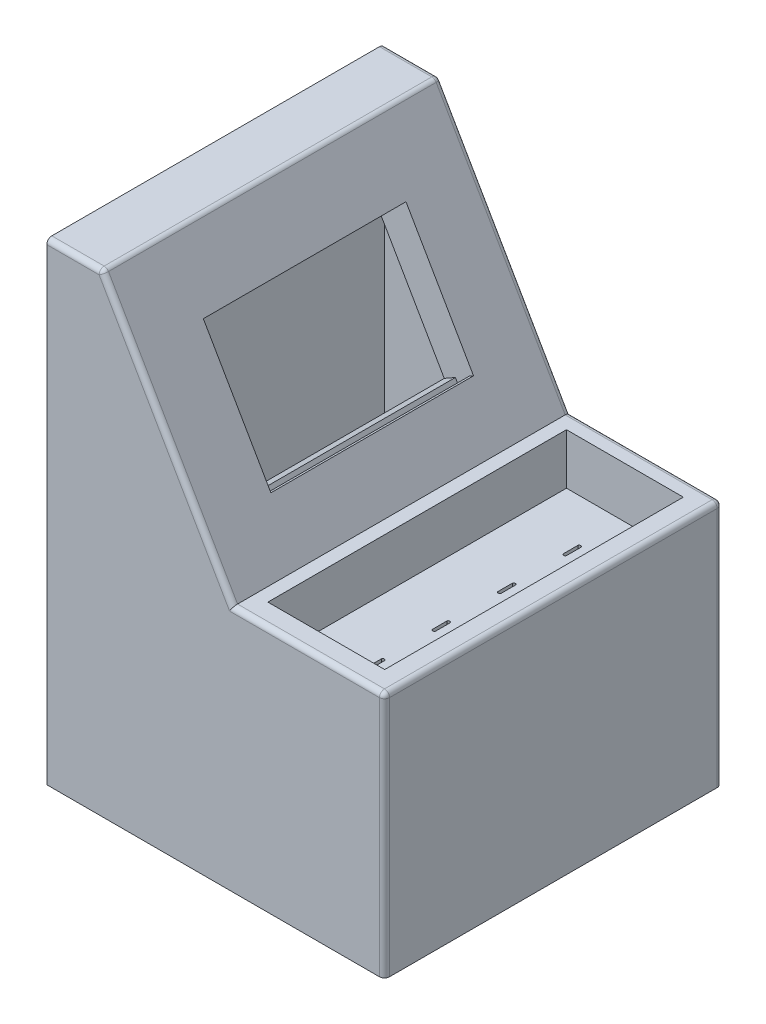
SolidWorks part; units mm, degrees
material "Polyethylene Cross-Linked"
ref_plane "Front Plane" through (0, 0, 0) normal (0, 0, 1) x (1, 0, 0)
ref_plane "Top Plane" through (0, 0, 0) normal (0, 1, 0) x (1, 0, 0)
ref_plane "Right Plane" through (0, 0, 0) normal (1, 0, 0) x (0, 0, -1)
sketch "Sketch1" plane through (0, 0, 0) normal (0, 0, 1) x (1, 0, 0)
  line L0 (0, 203.2) -> (0, 711.2)
  line L1 (0, 0) -> (508, 0)
  line L2 (0, 0) -> (0, 203.2)
  line L3 (0, 203.2) -> (508, 203.2)
  line L4 (508, 0) -> (508, 203.2)
  line L5 (0, 711.2) -> (83.1288, 711.2)
  line L6 (83.1288, 711.2) -> (279.4, 371.2483)
  line L7 (279.4, 371.2483) -> (508, 371.2483)
  line L8 (508, 371.2483) -> (508, 203.2)
  dimension "D1" = 508
  dimension "D2" = 508
  dimension "D3" = 203.2
  dimension "D4" = 120
  dimension "D5" = 392.5424
  dimension "D6" = 228.6
extrude "Boss-Extrude1" add sketch "Sketch1" along normal blind 508 contours L8 L7 L6 L5 L0 L3 | L2 L1 L4 L3 region at (189.225, 380.8468, 0)
sketch "Sketch2" plane through (0, 371.2483, 0) normal (0, 1, 0) x (1, 0, 0)
  line L1 (299.6447, -25.9057) -> (475.366, -25.9057)
  line L2 (299.6447, -25.9057) -> (299.6447, -475.0665)
  line L3 (299.6447, -475.0665) -> (475.366, -475.0665)
  line L4 (475.366, -25.9057) -> (475.366, -475.0665)
extrude "Cut-Extrude1" cut sketch "Sketch2" against normal blind 76.2
sketch "Sketch3" plane through (370.3053, 213.7958, 0) normal (0.866, 0.5, 0) x (0, 0, -1)
  line L0 (0, 574.3529) -> (0, 181.8105) construction
  line L1 (-406.4, 472.7529) -> (-101.6, 472.7529)
  line L2 (-406.4, 472.7529) -> (-406.4, 269.5529)
  line L3 (-406.4, 269.5529) -> (-101.6, 269.5529)
  line L4 (-101.6, 472.7529) -> (-101.6, 269.5529)
  line L7 (-508, 574.3529) -> (0, 574.3529) construction
  dimension "D1" = 203.2
  dimension "D2" = 304.8
  dimension "D3" = 101.6
  dimension "D4" = 101.6
extrude "Cut-Extrude3" cut sketch "Sketch3" against normal blind 50.8
shell "Shell2" thickness 27.94 removed face at (140.7347, 509.8236, 254)
fillet "Fillet1" radius 7.62 10 edges at (41.5644, 711.2, 508) (181.2644, 541.2242, 508) (393.7, 371.2483, 508) (508, 185.6242, 508) (83.1288, 711.2, 254) (41.5644, 711.2, 0) (181.2644, 541.2242, 0) (393.7, 371.2483, 0) (508, 185.6242, 0) (508, 371.2483, 254)
sketch "Sketch6" plane through (0, 0, 406.4) normal (0, 0, -1) x (-1, 0, 0)
  line L0 (-109.7118, 652.4423) -> (-240.0209, 424.215)
  line L1 (-275.0006, 363.6283) -> (-78.7294, 703.58) construction
  line L2 (-240.0209, 424.215) -> (-218.4495, 411.8986)
  line L3 (-218.4495, 411.8986) -> (-97.8271, 645.6566)
  line L4 (-97.8271, 645.6566) -> (-109.7118, 652.4423)
extrude "Cut-Extrude4" cut sketch "Sketch6" along normal up to surface (304.8 mm away) and the other way blind 97.536 up to face at (162.7318, 522.5236, 101.6)
ref_plane "Plane1" through (135.8523, 0, 0) normal (-1, 0, 0) x (0, 0, 1)
sketch "Sketch8" plane through (135.8523, 0, 0) normal (-1, 0, 0) x (0, 0, 1)
  line L4 (480.06, 267.1083) -> (480.06, 343.3083)
  line L5 (480.06, 343.3083) -> (27.94, 343.3083)
  line L6 (27.94, 343.3083) -> (27.94, 267.1083)
  line L7 (27.94, 267.1083) -> (480.06, 267.1083)
  line L8 (480.06, 267.1083) -> (480.06, 343.3083)
  line L9 (480.06, 343.3083) -> (27.94, 343.3083)
  line L10 (27.94, 343.3083) -> (27.94, 267.1083)
  line L11 (27.94, 267.1083) -> (480.06, 267.1083)
  dimension "D1" = 0
sketch "Sketch9" plane through (0, 295.0483, 0) normal (0, 1, 0) x (1, 0, 0)
sketch "Sketch10" plane through (0, 295.0483, 0) normal (0, 1, 0) x (1, 0, 0)
  line L0 (384.682, -385.4514) -> (385.482, -385.4514) construction
  line L1 (382.682, -408.9514) -> (382.682, -387.4514) construction
  line L2 (387.482, -387.4514) -> (387.482, -408.9514) construction
  line L3 (385.482, -410.9514) -> (384.682, -410.9514) construction
  line L4 (385.482, -312.4389) -> (384.682, -312.4389) construction
  line L5 (387.482, -288.9389) -> (387.482, -310.4389) construction
  line L6 (382.682, -310.4389) -> (382.682, -288.9389) construction
  line L7 (384.682, -286.9389) -> (385.482, -286.9389) construction
  line L8 (385.482, -213.9263) -> (384.682, -213.9263) construction
  line L9 (382.682, -211.9263) -> (382.682, -190.4263) construction
  line L10 (387.482, -190.4263) -> (387.482, -211.9263) construction
  line L11 (384.682, -188.4263) -> (385.482, -188.4263) construction
  line L12 (385.482, -115.4137) -> (384.682, -115.4137) construction
  line L13 (382.682, -113.4137) -> (382.682, -91.9137) construction
  line L14 (384.682, -89.9137) -> (385.482, -89.9137) construction
  line L15 (387.482, -91.9137) -> (387.482, -113.4137) construction
  line L16 (384.682, -385.4514) -> (385.482, -385.4514)
  line L17 (382.682, -408.9514) -> (382.682, -387.4514)
  line L18 (387.482, -387.4514) -> (387.482, -408.9514)
  line L19 (385.482, -410.9514) -> (384.682, -410.9514)
  line L20 (385.482, -312.4389) -> (384.682, -312.4389)
  line L21 (387.482, -288.9389) -> (387.482, -310.4389)
  line L22 (382.682, -310.4389) -> (382.682, -288.9389)
  line L23 (384.682, -286.9389) -> (385.482, -286.9389)
  line L24 (385.482, -213.9263) -> (384.682, -213.9263)
  line L25 (382.682, -211.9263) -> (382.682, -190.4263)
  line L26 (387.482, -190.4263) -> (387.482, -211.9263)
  line L27 (384.682, -188.4263) -> (385.482, -188.4263)
  line L28 (385.482, -115.4137) -> (384.682, -115.4137)
  line L29 (382.682, -113.4137) -> (382.682, -91.9137)
  line L30 (384.682, -89.9137) -> (385.482, -89.9137)
  line L31 (387.482, -91.9137) -> (387.482, -113.4137)
  arc A0 (387.482, -387.4514) -> (385.482, -385.4514) centre (385.482, -387.4514) ccw construction
  arc A1 (384.682, -385.4514) -> (382.682, -387.4514) centre (384.682, -387.4514) ccw construction
  arc A2 (385.482, -410.9514) -> (387.482, -408.9514) centre (385.482, -408.9514) ccw construction
  arc A3 (382.682, -408.9514) -> (384.682, -410.9514) centre (384.682, -408.9514) ccw construction
  arc A4 (385.482, -312.4389) -> (387.482, -310.4389) centre (385.482, -310.4389) ccw construction
  arc A5 (382.682, -310.4389) -> (384.682, -312.4389) centre (384.682, -310.4389) ccw construction
  arc A6 (384.682, -286.9389) -> (382.682, -288.9389) centre (384.682, -288.9389) ccw construction
  arc A7 (387.482, -288.9389) -> (385.482, -286.9389) centre (385.482, -288.9389) ccw construction
  arc A8 (385.482, -213.9263) -> (387.482, -211.9263) centre (385.482, -211.9263) ccw construction
  arc A9 (382.682, -211.9263) -> (384.682, -213.9263) centre (384.682, -211.9263) ccw construction
  arc A10 (387.482, -190.4263) -> (385.482, -188.4263) centre (385.482, -190.4263) ccw construction
  arc A11 (384.682, -188.4263) -> (382.682, -190.4263) centre (384.682, -190.4263) ccw construction
  arc A12 (382.682, -113.4137) -> (384.682, -115.4137) centre (384.682, -113.4137) ccw construction
  arc A13 (385.482, -115.4137) -> (387.482, -113.4137) centre (385.482, -113.4137) ccw construction
  arc A14 (384.682, -89.9137) -> (382.682, -91.9137) centre (384.682, -91.9137) ccw construction
  arc A15 (387.482, -91.9137) -> (385.482, -89.9137) centre (385.482, -91.9137) ccw construction
  arc A16 (387.482, -387.4514) -> (385.482, -385.4514) centre (385.482, -387.4514) ccw
  arc A17 (384.682, -385.4514) -> (382.682, -387.4514) centre (384.682, -387.4514) ccw
  arc A18 (385.482, -410.9514) -> (387.482, -408.9514) centre (385.482, -408.9514) ccw
  arc A19 (382.682, -408.9514) -> (384.682, -410.9514) centre (384.682, -408.9514) ccw
  arc A20 (385.482, -312.4389) -> (387.482, -310.4389) centre (385.482, -310.4389) ccw
  arc A21 (382.682, -310.4389) -> (384.682, -312.4389) centre (384.682, -310.4389) ccw
  arc A22 (384.682, -286.9389) -> (382.682, -288.9389) centre (384.682, -288.9389) ccw
  arc A23 (387.482, -288.9389) -> (385.482, -286.9389) centre (385.482, -288.9389) ccw
  arc A24 (385.482, -213.9263) -> (387.482, -211.9263) centre (385.482, -211.9263) ccw
  arc A25 (382.682, -211.9263) -> (384.682, -213.9263) centre (384.682, -211.9263) ccw
  arc A26 (387.482, -190.4263) -> (385.482, -188.4263) centre (385.482, -190.4263) ccw
  arc A27 (384.682, -188.4263) -> (382.682, -190.4263) centre (384.682, -190.4263) ccw
  arc A28 (382.682, -113.4137) -> (384.682, -115.4137) centre (384.682, -113.4137) ccw
  arc A29 (385.482, -115.4137) -> (387.482, -113.4137) centre (385.482, -113.4137) ccw
  arc A30 (384.682, -89.9137) -> (382.682, -91.9137) centre (384.682, -91.9137) ccw
  arc A31 (387.482, -91.9137) -> (385.482, -89.9137) centre (385.482, -91.9137) ccw
extrude "Cut-Extrude5" cut sketch "Sketch10" against normal up to next contours A16 L16 A17 L17 A19 L19 A18 L18 | A20 L21 A23 L23 A22 L22 A21 L20 | L24 A25 L25 A27 L27 A26 L26 A24 | A28 L28 A29 L31 A31 L30 A30 L29
